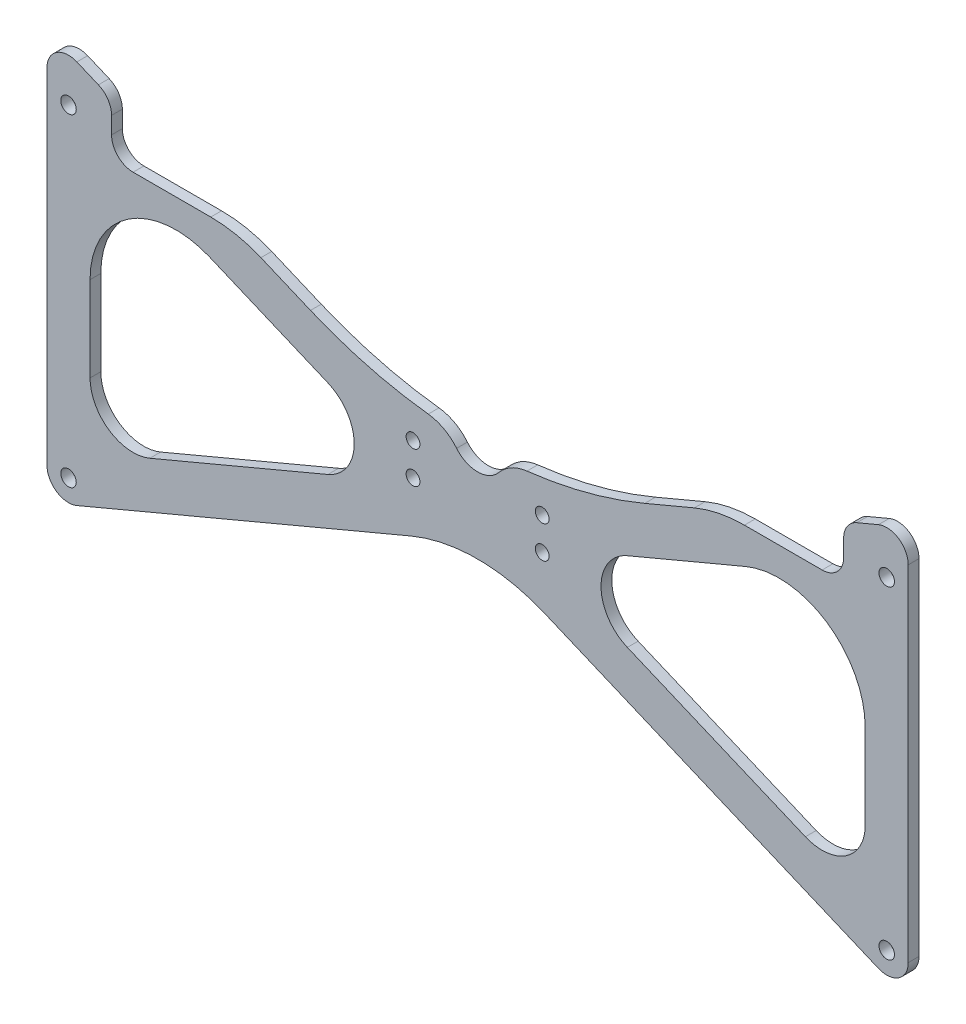
SolidWorks part; units mm, degrees
ref_plane "Front Plane" through (0, 0, 0) normal (0, 0, 1) x (1, 0, 0)
ref_plane "Top Plane" through (0, 0, 0) normal (0, 1, 0) x (1, 0, 0)
ref_plane "Right Plane" through (0, 0, 0) normal (1, 0, 0) x (0, 0, -1)
sketch "Sketch1" plane through (0, 0, 0) normal (0, 0, 1) x (1, 0, 0)
  line L0 (-120.65, -50.8) -> (120.65, 50.8) construction
  line L3 (-114.3, -41.2364) -> (-16.3636, 0)
  line L11 (-120.65, 50.8) -> (120.65, -50.8) construction
  line L12 (-118.1858, 56.6524) -> (0, 6.8899)
  line L13 (-114.3, 41.2364) -> (-16.3636, 0)
  line L14 (0, 6.8899) -> (118.1858, 56.6524)
  line L16 (16.3636, 0) -> (114.3, 41.2364)
  line L17 (16.3636, 0) -> (114.3, -41.2364)
  line L18 (-127, 50.8) -> (-127, -50.8)
  line L19 (-114.3, 41.2364) -> (-114.3, -41.2364)
  line L20 (127, 50.8) -> (127, -50.8)
  line L21 (114.3, 41.2364) -> (114.3, -41.2364)
  line L28 (-118.1858, -56.6524) -> (0, -6.8899)
  line L30 (0, -6.8899) -> (118.1858, -56.6524)
  arc A4 (-127, -50.8) -> (-118.1858, -56.6524) centre (-120.65, -50.8) ccw
  arc A5 (127, 50.8) -> (118.1858, 56.6524) centre (120.65, 50.8) ccw
  arc A6 (-118.1858, 56.6524) -> (-127, 50.8) centre (-120.65, 50.8) ccw
  arc A7 (118.1858, -56.6524) -> (127, -50.8) centre (120.65, -50.8) ccw
  point P2 (0, 0)
  point P9 (0, 0)
  point P13 (0, 0)
  point P26 (0, 0)
  dimension "D1" = 254
  dimension "D3" = 6.35
  dimension "D2" = 101.6
  dimension "D5" = 12.7
extrude "Boss-Extrude1" add sketch "Sketch1" along normal blind 3.175
sketch "Sketch2" plane through (0, 0, 3.175) normal (0, 0, 1) x (1, 0, 0)
  circle A0 centre (-120.65, 44.45) radius 2.286
  circle A1 centre (-120.65, -50.8) radius 2.286
  circle A2 centre (120.65, -50.8) radius 2.286
  circle A3 centre (120.65, 44.45) radius 2.286
  arc A5 (-127, -50.8) -> (-118.1858, -56.6524) centre (-120.65, -50.8) ccw construction
  arc A6 (118.1858, -56.6524) -> (127, -50.8) centre (120.65, -50.8) ccw construction
  circle A8 centre (-120.65, 44.45) radius 1.905 construction
  circle A9 centre (120.65, 44.45) radius 1.905 construction
  dimension "D1" = 4.572
extrude "Cut-Extrude1" cut sketch "Sketch2" against normal through all
fillet "Fillet1" radius 12.7 4 edges at (114.3, -41.2364, 1.5875) (16.3636, 0, 1.5875) (-114.3, -41.2364, 1.5875) (-16.3636, 0, 1.5875)
fillet "Fillet5" radius 127 1 edges at (0, 6.8899, 1.5875)
fillet "Fillet8" radius 25.4 2 edges at (114.3, 41.2364, 1.5875) (-114.3, 41.2364, 1.5875)
fillet "Fillet10" radius 50.8 1 edges at (0, -6.8899, 1.5875)
sketch "Sketch5" plane through (0, 0, 3.175) normal (0, 0, 1) x (1, 0, 0)
  circle A0 centre (-19.05, 9.525) radius 2.032
  circle A1 centre (-19.05, 0) radius 2.032
  point P4 (-19.05, 7.8842)
  dimension "D2" = 4.064
  dimension "D1" = 9.525
  dimension "D3" = 19.05
  dimension "D4" = 9.525
extrude "Cut-Extrude3" cut sketch "Sketch5" against normal through all
mirror "Mirror1" about plane through (0, 0, 0) normal (1, 0, 0) of "Cut-Extrude3"
sketch "Sketch6" plane through (0, 0, 3.175) normal (0, 0, 1) x (1, 0, 0)
  line L6 (-107.95, 52.3426) -> (-107.95, 36.7851)
  line L8 (-49.2832, 27.6408) -> (-118.1858, 56.6524) construction
  line L9 (-107.95, 36.7851) -> (-71.0009, 36.7851)
  line L12 (-127, 50.8) -> (-127, -50.8) construction
  line L13 (-71.0009, 36.7851) -> (-107.95, 52.3426)
  dimension "D1" = 15.5575
  dimension "D2" = 19.05
extrude "Cut-Extrude4" cut sketch "Sketch6" against normal through all contours L6 L9 L13
mirror "Mirror2" about plane through (0, 0, 0) normal (1, 0, 0) of "Cut-Extrude4"
fillet "Fillet6" radius 6.35 4 edges at (-107.95, 52.3426, 1.5875) (-107.95, 36.7851, 1.5875) (107.95, 52.3426, 1.5875) (107.95, 36.7851, 1.5875)
fillet "Fillet9" radius 38.1 2 edges at (71.0009, 36.7851, 1.5875) (-71.0009, 36.7851, 1.5875)
sketch "Sketch7" plane through (0, 0, 3.175) normal (0, 0, 1) x (1, 0, 0)
  arc A0 (-7.9375, 17.9367) -> (7.9375, 17.9367) centre (0, 19.05) ccw
  arc A2 (-49.2832, 27.6408) -> (49.2832, 27.6408) centre (0, 144.6885) ccw construction
  arc A3 (-7.9375, 17.9367) -> (7.9375, 17.9367) centre (0, 144.6885) ccw
  point P6 (0, 0)
  dimension "D1" = 19.05
  dimension "D2" = 15.875
extrude "Cut-Extrude5" cut sketch "Sketch7" against normal through all
fillet "Fillet11" radius 12.7 2 edges at (7.9375, 17.9367, 1.5875) (-7.9375, 17.9367, 1.5875)
